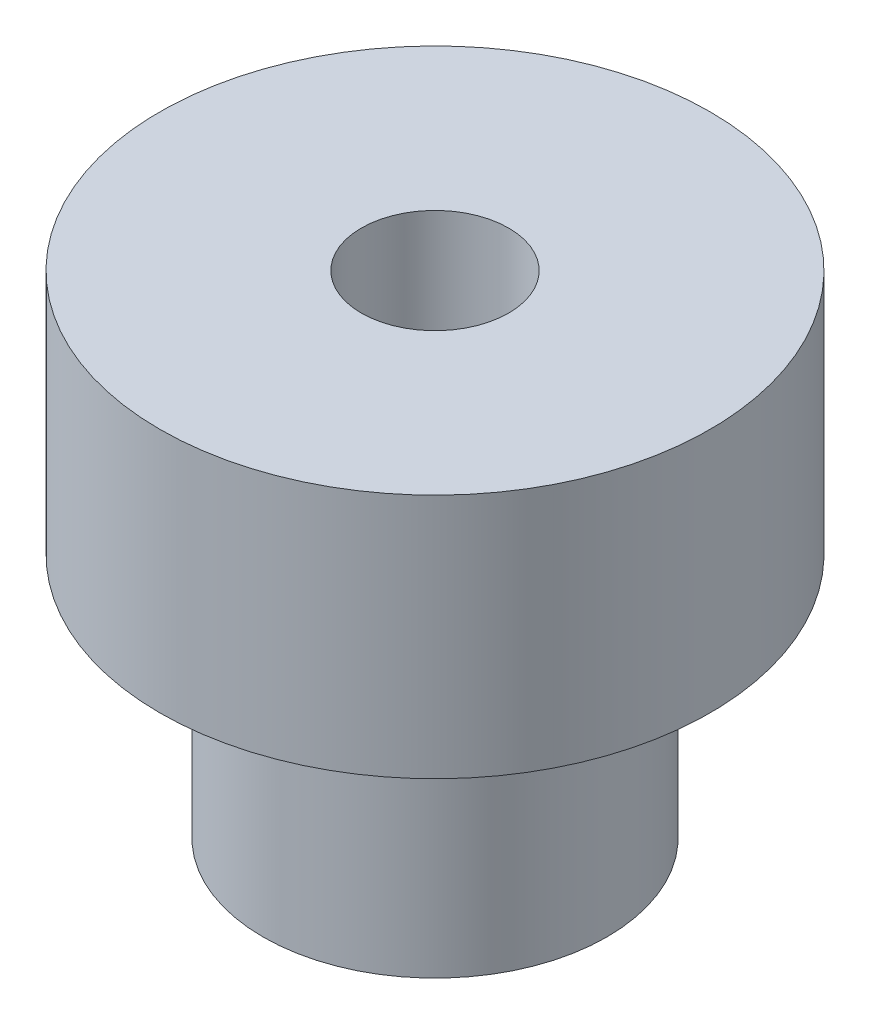
SolidWorks part; units mm, degrees
ref_plane "Front Plane" through (0, 0, 0) normal (0, 0, 1) x (1, 0, 0)
ref_plane "Top Plane" through (0, 0, 0) normal (0, 1, 0) x (1, 0, 0)
ref_plane "Right Plane" through (0, 0, 0) normal (1, 0, 0) x (0, 0, -1)
sketch "Sketch1" plane through (0, 0, 0) normal (0, 1, 0) x (1, 0, 0)
  circle A0 centre (0, 0) radius 5.6
  circle A1 centre (0, 0) radius 1.5
  dimension "D1" = 11.2
  dimension "D2" = 3
extrude "Boss-Extrude1" add sketch "Sketch1" along normal blind 5
sketch "Sketch2" plane through (0, 0, 0) normal (0, -1, 0) x (1, 0, 0)
  circle A0 centre (0, 0) radius 3.5
  circle A1 centre (0, 0) radius 1.5
  dimension "D1" = 7
extrude "Boss-Extrude2" add sketch "Sketch2" along normal blind 5
